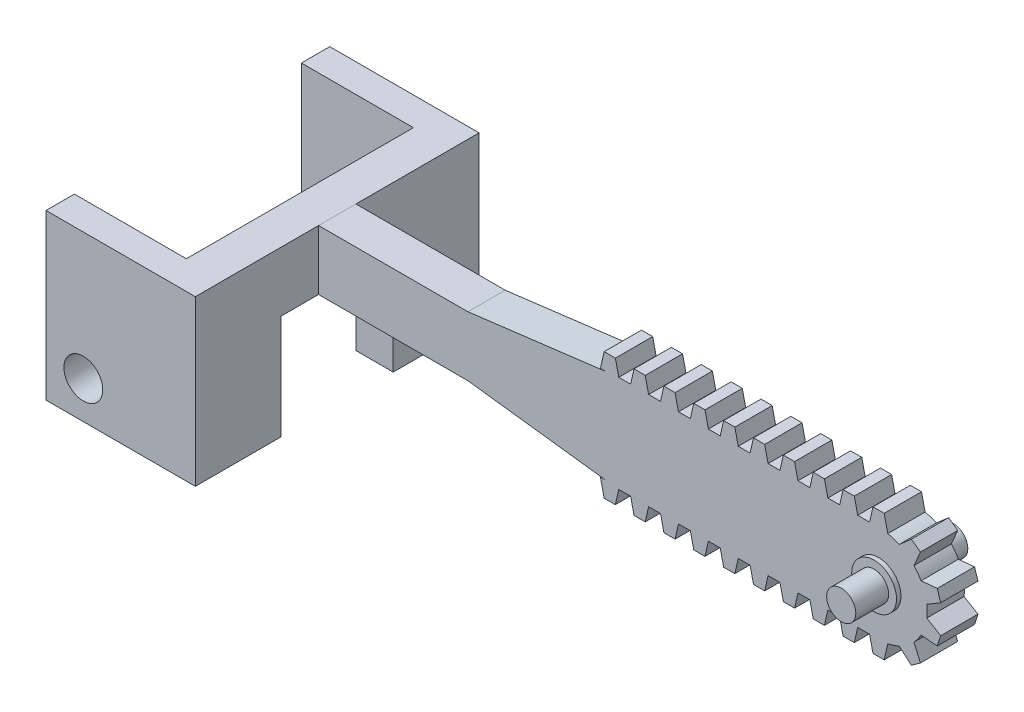
SolidWorks part; units mm, degrees
ref_plane "Front Plane" through (0, 0, 0) normal (0, 0, 1) x (1, 0, 0)
ref_plane "Top Plane" through (0, 0, 0) normal (0, 1, 0) x (1, 0, 0)
ref_plane "Right Plane" through (0, 0, 0) normal (1, 0, 0) x (0, 0, -1)
sketch "Esquisse1" plane through (0, 0, 0) normal (0, 0, 1) x (1, 0, 0)
  line L0 (-17.5, 6.5) -> (-37.5, 4)
  line L1 (-17.5, 6.5) -> (17.5, 6.5)
  line L2 (-37.5, 4) -> (-57.5, 4)
  line L3 (-17.5, -6.5) -> (17.5, -6.5)
  line L4 (-57.5, 4) -> (-57.5, -4)
  line L5 (-57.5, -4) -> (-37.5, -4)
  line L6 (-37.5, -4) -> (-17.5, -6.5)
  line L7 (55, 0) -> (-55, 0) construction
  arc A0 (17.5, 6.5) -> (17.5, -6.5) centre (17.5, 0) cw
  point P6 (0, -6.5)
  point P7 (-7.2041, 6.5)
  point P10 (-27.5, -2.4702)
  point P13 (-57.5, 0)
  dimension "D1" = 13
  dimension "D2" = 35
  dimension "D3" = 8
  dimension "D4" = 20
  dimension "D5" = 20
extrude "Boss.-Extru.1" add sketch "Esquisse1" along normal mid plane 5
sketch "Esquisse2" plane through (0, 0, 0) normal (0, 0, 1) x (1, 0, 0)
  circle A0 centre (17.5, 0) radius 1.95
  arc A1 (17.5, -6.5) -> (17.5, 6.5) centre (17.5, 0) ccw construction
  point P2 (0, 0)
  point P4 (0, 0)
  point P6 (17.3208, 0)
  dimension "D1" = 3.9
extrude "Boss.-Extru.2" add sketch "Esquisse2" along normal mid plane 15
sketch "Esquisse5" plane through (0, 0, 0) normal (0, 0, 1) x (1, 0, 0)
  line L0 (16.25, -6.3) -> (16.75, -8.5)
  line L1 (16.75, -8.5) -> (18.25, -8.5)
  line L2 (18.25, -8.5) -> (18.75, -6.3)
  line L4 (18.75, -6.3) -> (16.25, -6.3)
  line L6 (-17.5, -6.5) -> (17.5, -6.5) construction
  point P4 (-7.9208, -6.5)
  point P7 (17.5, -6.3)
  point P8 (20.5699, -6.5)
  point P9 (23.3966, -6.5)
  point P10 (18.6351, -6.5)
  point P14 (0, 0)
  dimension "D1" = 1.5
  dimension "D2" = 2.2
  dimension "D3" = 2.5
  dimension "D4" = 0.2
extrude "Boss.-Extru.3" add sketch "Esquisse5" along normal mid plane 5
pattern_linear "Répétition linéaire1" count 10 spacing 4 along (-1, 0, 0) of "Boss.-Extru.3"
mirror "Symétrie1" about plane through (0, 0, 0) normal (0, 1, 0) of "Répétition linéaire1"
pattern_circular "Répétition circulaire1" count 6 every 36 about axis through (17.5, 0, 2.5) along (0, 0, 1) of "Boss.-Extru.3"
sketch "Esquisse6" plane through (0, 0, 2.5) normal (0, 0, 1) x (1, 0, 0)
  circle A0 centre (17.5, 0) radius 3
  circle A1 centre (17.5, 0) radius 1.95 construction
  point P2 (0, 0)
  dimension "D1" = 6
extrude "Boss.-Extru.4" add sketch "Esquisse6" along normal blind 0.6
sketch "Esquisse7" plane through (0, 0, -2.5) normal (0, 0, -1) x (-1, 0, 0)
  circle A0 centre (-17.5, 0) radius 3
  circle A1 centre (-17.5, 0) radius 1.95 construction
  dimension "D1" = 6
extrude "Boss.-Extru.5" add sketch "Esquisse7" along normal blind 0.6
sketch "Esquisse10" plane through (0, 4, 0) normal (0, 1, 0) x (1, 0, 0)
  line L0 (-57.5, -2.5) -> (-57.5, 2.5) construction
  line L1 (-57.5, -19) -> (-77.5, -19)
  line L2 (-77.5, -19) -> (-77.5, -15.2)
  line L3 (-77.5, -15.2) -> (-62.5, -15.2)
  line L4 (-62.5, -15.2) -> (-62.5, 15.2)
  line L5 (-62.5, 15.2) -> (-77.5, 15.2)
  line L6 (-77.5, 15.2) -> (-77.5, 19)
  line L7 (-77.5, 19) -> (-57.5, 19)
  line L8 (-57.5, 19) -> (-57.5, -19)
  point P0 (-71.0349, -1.3948)
  point P12 (-67.5, -2.5)
  point P14 (-57.5, 0)
  point P15 (-57.5, 0)
  dimension "D1" = 38
  dimension "D2" = 3.8
  dimension "D3" = 5
  dimension "D4" = 15
extrude "Boss.-Extru.6" add sketch "Esquisse10" against normal blind 22 separate body
sketch "Esquisse11" plane through (0, 0, 19) normal (0, 0, 1) x (1, 0, 0)
  line L0 (-77.5, -18) -> (-77.5, 4) construction
  line L2 (-77.5, -18) -> (-57.5, -18) construction
  circle A0 centre (-72.5, -13) radius 2.6
  dimension "D1" = 5.2
  dimension "D2" = 5
  dimension "D3" = 5
extrude "Enlèv. mat.-Extru.5" cut sketch "Esquisse11" against normal through all
sketch "Esquisse12" plane through (-57.5, 0, 0) normal (1, 0, 0) x (0, 0, -1)
  line L0 (-19, -18) -> (19, -18) construction
  line L1 (7.5, -4) -> (-7.5, -4)
  line L2 (7.5, -4) -> (7.5, -18)
  line L3 (7.5, -18) -> (-7.5, -18)
  line L4 (-7.5, -4) -> (-7.5, -18)
  point P6 (3.6691, -17.5)
  point P7 (0, -18)
  point P8 (0, -18)
  dimension "D1" = 15
extrude "Enlèv. mat.-Extru.6" cut sketch "Esquisse12" against normal through all
